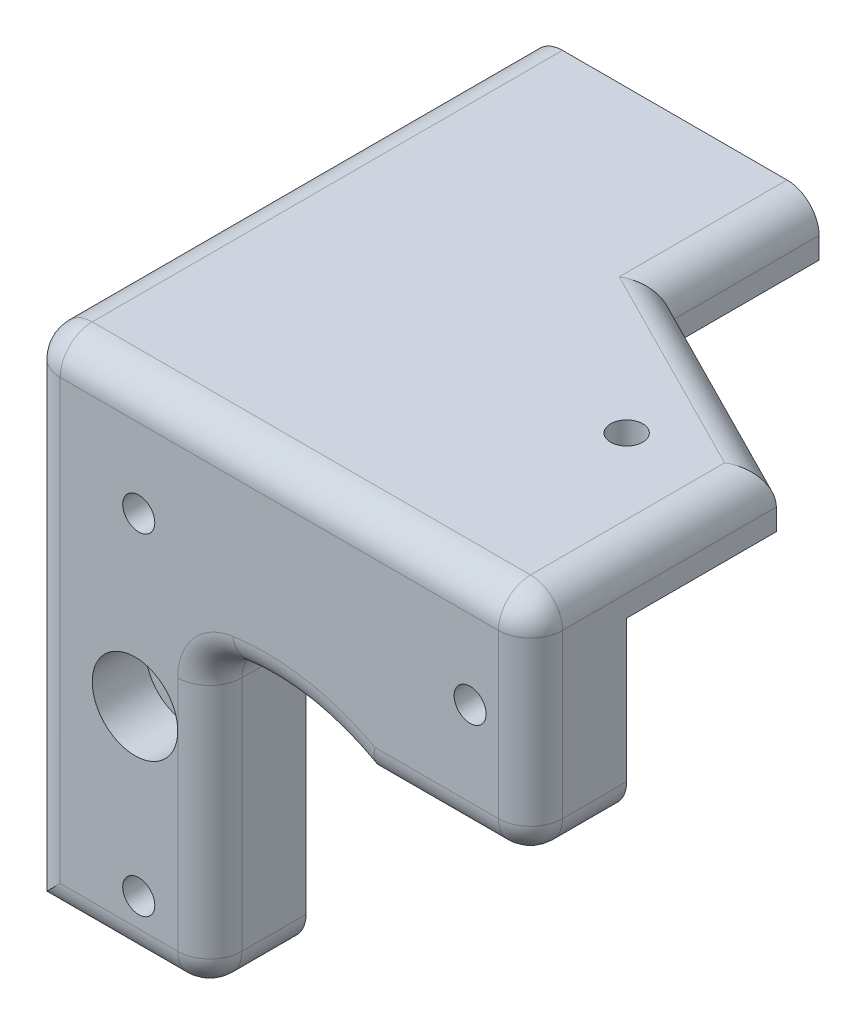
SolidWorks part; units mm, degrees
ref_plane "Front Plane" through (0, 0, 0) normal (0, 0, 1) x (1, 0, 0)
ref_plane "Top Plane" through (0, 0, 0) normal (0, 1, 0) x (1, 0, 0)
ref_plane "Right Plane" through (0, 0, 0) normal (1, 0, 0) x (0, 0, -1)
sketch "Sketch2" plane through (0, 0, 0) normal (0, 0, 1) x (1, 0, 0)
  line L0 (0, 0) -> (0, 47)
  line L1 (0, 47) -> (47, 47)
  line L2 (47, 47) -> (47, 25.75)
  line L3 (47, 25.75) -> (31.68, 25.75)
  line L4 (17, 0) -> (17, 27.58)
  line L5 (17, 0) -> (0, 0)
  arc A0 (17, 27.58) -> (31.68, 25.75) centre (22.2111, 9.5871) cw
  dimension "D1" = 47
  dimension "D2" = 47
  dimension "D3" = 21.25
  dimension "D4" = 17
  dimension "D5" = 27.58
  dimension "D6" = 15.32
extrude "Boss-Extrude1" add sketch "Sketch2" along normal blind 9
sketch "Sketch3" plane through (0, 0, 9) normal (0, 0, 1) x (1, 0, 0)
  line L0 (0, 0) -> (17, 0) construction
  line L1 (0, 47) -> (0, 0) construction
  line L3 (47, 47) -> (0, 47) construction
  circle A0 centre (10.35, 5.65) radius 1.5
  circle A1 centre (10.35, 36.65) radius 1.5
  circle A2 centre (41.35, 36.65) radius 1.5
  dimension "D1" = 3
  dimension "D5" = 3
  dimension "D6" = 3
  dimension "D2" = 5.65
  dimension "D3" = 10.35
  dimension "D4" = 31
  dimension "D7" = 10.35
  dimension "D8" = 31
extrude "Cut-Extrude1" cut sketch "Sketch3" against normal blind 10
sketch "Sketch8" plane through (0, 0, 0) normal (0, 0, -1) x (-1, 0, 0)
  line L0 (0, 0) -> (-17, 0) construction
  line L1 (0, 47) -> (-5, 47)
  line L2 (0, 47) -> (0, 0)
  line L3 (0, 0) -> (-5, 0)
  line L4 (-5, 47) -> (-5, 0)
  dimension "D1" = 5
extrude "Boss-Extrude2" add sketch "Sketch8" along normal blind 38
sketch "Sketch9" plane through (0, 0, 0) normal (0, 0, -1) x (-1, 0, 0)
  line L0 (-47, 25.75) -> (-47, 47) construction
  line L1 (-5, 47) -> (-47, 47)
  line L2 (-5, 47) -> (-5, 42)
  line L3 (-5, 42) -> (-47, 42)
  line L4 (-47, 47) -> (-47, 42)
  dimension "D1" = 5
extrude "Boss-Extrude3" add sketch "Sketch9" along normal blind 38
sketch "Sketch10" plane through (0, 0, 0) normal (-1, 0, 0) x (0, 0, 1)
  line L0 (0, 0) -> (-23, 32)
  line L1 (-23, 32) -> (-38, 32)
  line L2 (-38, 0) -> (-38, 47) construction
  line L3 (-38, 32) -> (-38, 0)
  line L4 (-38, 0) -> (0, 0)
  dimension "D1" = 15
  dimension "D2" = 15
extrude "Cut-Extrude2" cut sketch "Sketch10" against normal blind 38
sketch "Sketch11" plane through (0, 0, 9) normal (0, 0, 1) x (1, 0, 0)
  line L0 (0, 47) -> (0, 0) construction
  line L4 (47, 47) -> (0, 47) construction
  circle A0 centre (10, 20.85) radius 4
  dimension "D1" = 8
  dimension "D2" = 10
  dimension "D3" = 26.15
extrude "Cut-Extrude3" cut sketch "Sketch11" against normal blind 5
sketch "Sketch12" plane through (0, 42, 0) normal (0, -1, 0) x (1, 0, 0)
  line L0 (47, -38) -> (47, -14)
  line L1 (47, -38) -> (47, 0) construction
  line L2 (47, -14) -> (27, -24.1488)
  line L3 (27, -24.1488) -> (27, -38)
  line L4 (47, -38) -> (5, -38) construction
  line L5 (27, -38) -> (47, -38)
  dimension "D1" = 14
  dimension "D2" = 20
extrude "Cut-Extrude4" cut sketch "Sketch12" against normal blind 10
sketch "Sketch13" plane through (0, 42, 0) normal (0, -1, 0) x (1, 0, 0)
  line L0 (47, -14) -> (47, 0) construction
  line L1 (47, 0) -> (5, 0) construction
  circle A0 centre (37, -10) radius 1.5
  dimension "D1" = 3
  dimension "D2" = 10
  dimension "D3" = 10
extrude "Cut-Extrude5" cut sketch "Sketch13" against normal through all
sketch "Sketch14" plane through (0, 42, 0) normal (0, -1, 0) x (-1, 0, 0)
  circle A0 centre (-37, 10) radius 3
  dimension "D1" = 6
extrude "Cut-Extrude6" cut sketch "Sketch14" against normal blind 2
fillet "Fillet1" radius 3 16 edges at (47, 25.75, 4.5) (17, 0, 4.5) (8.5, 0, 9) (17, 27.58, 4.5) (39.34, 25.75, 9) (24.5283, 28.1755, 9) (17, 13.79, 9) (47, 36.375, 9) (47, 47, -2.5) (37, 47, -19.0744) (27, 47, -31.0744) (0, 32, -30.5) (0, 16, -11.5) (0, 23.5, 9) (23.5, 47, 9) (0, 47, -14.5)
